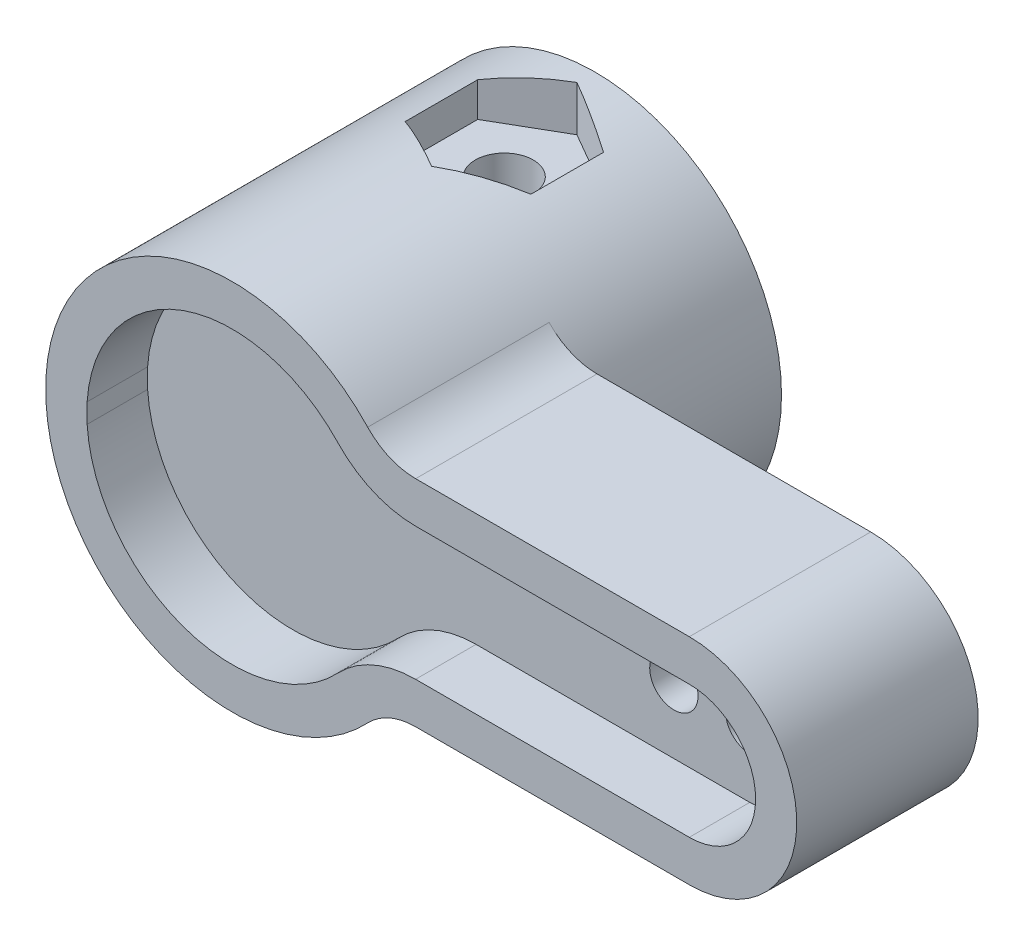
SolidWorks part; units mm, degrees
ref_plane "Front Plane" through (0, 0, 0) normal (0, 0, 1) x (1, 0, 0)
ref_plane "Top Plane" through (0, 0, 0) normal (0, 1, 0) x (1, 0, 0)
ref_plane "Right Plane" through (0, 0, 0) normal (1, 0, 0) x (0, 0, -1)
sketch "Sketch4" plane through (0, 0, 0) normal (0, 0, 1) x (1, 0, 0)
  line L0 (27.6867, 9.4129) -> (31.6042, 9.4129) construction
  line L1 (31.6042, 8.4129) -> (27.6867, 8.4129) construction
  line L2 (20.2537, 8.4129) -> (16.7375, 8.4129) construction
  line L3 (33.601, 5.8129) -> (47.9702, 5.8129)
  line L4 (47.9702, 12.0129) -> (33.601, 12.0129)
  line L5 (16.7375, 9.4129) -> (20.2537, 9.4129) construction
  line L6 (16.7375, 9.4129) -> (16.7375, 8.4129)
  line L7 (16.3565, 9.4259) -> (16.3565, 8.3999)
  line L8 (33.601, 5.4319) -> (47.9702, 5.4319)
  line L9 (47.9702, 12.3939) -> (33.601, 12.3939)
  line L10 (14.1975, 9.494) -> (14.1975, 8.3318)
  line L11 (33.601, 3.2729) -> (47.9702, 3.2729)
  line L12 (47.9702, 14.5529) -> (33.601, 14.5529)
  arc A0 (27.6867, 9.4129) -> (20.2537, 9.4129) centre (23.9702, 8.9129) ccw construction
  arc A1 (31.6042, 8.4129) -> (31.6042, 9.4129) centre (32.4702, 8.9129) ccw construction
  arc A2 (20.2537, 8.4129) -> (27.6867, 8.4129) centre (23.9702, 8.9129) ccw construction
  arc A3 (16.7375, 8.4129) -> (29.2399, 3.9336) centre (23.9702, 8.9129) ccw
  arc A4 (33.601, 5.8129) -> (29.2399, 3.9336) centre (33.601, -0.1871) ccw
  arc A5 (47.9702, 5.8129) -> (47.9702, 12.0129) centre (47.9702, 8.9129) ccw
  arc A6 (29.2399, 13.8921) -> (33.601, 12.0129) centre (33.601, 18.0129) ccw
  arc A7 (29.2399, 13.8921) -> (16.7375, 9.4129) centre (23.9702, 8.9129) ccw
  arc A8 (16.3565, 8.3999) -> (29.5168, 3.672) centre (23.9702, 8.9129) ccw
  arc A9 (33.601, 5.4319) -> (29.5168, 3.672) centre (33.601, -0.1871) ccw
  arc A10 (47.9702, 5.4319) -> (47.9702, 12.3939) centre (47.9702, 8.9129) ccw
  arc A11 (29.5168, 14.1538) -> (33.601, 12.3939) centre (33.601, 18.0129) ccw
  arc A12 (29.5168, 14.1538) -> (16.3565, 9.4259) centre (23.9702, 8.9129) ccw
  arc A13 (14.1975, 8.3318) -> (31.0861, 2.1892) centre (23.9702, 8.9129) ccw
  arc A14 (33.601, 3.2729) -> (31.0861, 2.1892) centre (33.601, -0.1871) ccw
  arc A15 (47.9702, 3.2729) -> (47.9702, 14.5529) centre (47.9702, 8.9129) ccw
  arc A16 (31.0861, 15.6366) -> (33.601, 14.5529) centre (33.601, 18.0129) ccw
  arc A17 (31.0861, 15.6366) -> (14.1975, 9.494) centre (23.9702, 8.9129) ccw
  dimension "D1" = 0.381
  dimension "D2" = 2.54
extrude "Boss-Extrude3" add sketch "Sketch4" along normal blind 3.175 contours A16 A17 L10 A13 A14 L11 A15 L12 A12 A11 L9 A10 L8 A9 A8 L7 region at (20.7744, 17.6996, 0)
sketch "Sketch5" plane through (0, 0, 0) normal (0, 0, -1) x (-1, 0, 0)
  line L3 (-33.601, 14.5529) -> (-47.9702, 14.5529)
  line L4 (-47.9702, 3.2729) -> (-33.601, 3.2729)
  line L5 (-14.1975, 8.3318) -> (-14.1975, 9.494)
  line L6 (-33.601, 14.5529) -> (-47.9702, 14.5529)
  line L7 (-47.9702, 3.2729) -> (-33.601, 3.2729)
  line L8 (-14.1975, 8.3318) -> (-14.1975, 9.494)
  arc A5 (-33.601, 14.5529) -> (-31.0861, 15.6366) centre (-33.601, 18.0129) ccw
  arc A6 (-47.9702, 14.5529) -> (-47.9702, 3.2729) centre (-47.9702, 8.9129) ccw
  arc A7 (-31.0861, 2.1892) -> (-33.601, 3.2729) centre (-33.601, -0.1871) ccw
  arc A8 (-31.0861, 2.1892) -> (-14.1975, 8.3318) centre (-23.9702, 8.9129) ccw
  arc A9 (-14.1975, 9.494) -> (-31.0861, 15.6366) centre (-23.9702, 8.9129) ccw
  arc A10 (-33.601, 14.5529) -> (-31.0861, 15.6366) centre (-33.601, 18.0129) ccw
  arc A11 (-47.9702, 14.5529) -> (-47.9702, 3.2729) centre (-47.9702, 8.9129) ccw
  arc A12 (-31.0861, 2.1892) -> (-33.601, 3.2729) centre (-33.601, -0.1871) ccw
  arc A13 (-31.0861, 2.1892) -> (-14.1975, 8.3318) centre (-23.9702, 8.9129) ccw
  arc A14 (-14.1975, 9.494) -> (-31.0861, 15.6366) centre (-23.9702, 8.9129) ccw
  dimension "D1" = 0
extrude "Boss-Extrude4" add sketch "Sketch5" along normal blind 6.35
sketch "Sketch8" plane through (0, 0, -6.35) normal (0, 0, -1) x (-1, 0, 0)
  circle A0 centre (-47.9732, 8.9129) radius 1.27
  arc A1 (-47.9702, 14.5529) -> (-47.9702, 3.2729) centre (-47.9702, 8.9129) ccw construction
  arc A2 (-14.1975, 9.494) -> (-31.0861, 15.6366) centre (-23.9702, 8.9129) ccw construction
  circle A3 centre (-43.9854, 8.9129) radius 1.27
  point P7 (-53.6102, 8.9129)
  dimension "D1" = 2.54
  dimension "D2" = 24.003
  dimension "D3" = 3.9878
extrude "Cut-Extrude3" cut sketch "Sketch8" against normal up to next
sketch "Sketch9" plane through (0, 0, -6.35) normal (0, 0, -1) x (-1, 0, 0)
  line L1 (-18.3505, 3.2931) -> (-29.59, 3.2931)
  line L2 (-18.3505, 3.2931) -> (-18.3505, 14.5326)
  line L3 (-18.3505, 14.5326) -> (-29.59, 14.5326)
  line L4 (-29.59, 3.2931) -> (-29.59, 14.5326)
  line L5 (-18.3505, 3.2931) -> (-29.59, 14.5326) construction
  line L6 (-18.3505, 14.5326) -> (-29.59, 3.2931) construction
  circle A0 centre (-23.9702, 8.9129) radius 6.4135
  arc A1 (-14.1975, 9.494) -> (-31.0861, 15.6366) centre (-23.9702, 8.9129) ccw construction
  circle A2 centre (-23.9702, 8.9129) radius 9.79
  arc M10 (-31.0861, 2.1892) -> (-14.1975, 8.3318) centre (-23.9702, 8.9129) ccw
  line M11 (-14.1975, 8.3318) -> (-14.1975, 9.494)
  arc M12 (-14.1975, 9.494) -> (-31.0861, 15.6366) centre (-23.9702, 8.9129) ccw
  dimension "D1" = 12.827
  dimension "D2" = 11.2395
extrude "Boss-Extrude5" add sketch "Sketch9" along normal blind 9.525 contours A2 A0 L3 L2 L1 L4 M12 M10 M11 | A0 L3 L4 | L4 A0 | A0 L4 L1 | L1 A0 | A0 L1 L2 | L2 A0 | A0 L2 L3 | L3 A0 region at (19.1113, 4.054, -6.35) region at (23.9702, 2.9739, -6.35) region at (18.0312, 8.9129, -6.35) region at (28.8291, 4.054, -6.35) region at (19.1113, 13.7717, -6.35) region at (29.9092, 8.9129, -6.35) region at (23.9702, 14.8519, -6.35) region at (28.8291, 13.7717, -6.35) region at (14.4743, 8.9129, -6.35)
sketch "Sketch10" plane through (0, 0, 0) normal (0, 1, 0) x (1, 0, 0)
  line L1 (20.8797, 15.875) -> (27.0607, 15.875) construction
  line L3 (23.9702, 15.875) -> (23.9702, 6.35) construction
  line L4 (47.9702, 6.35) -> (33.601, 6.35) construction
  line L5 (20.8797, 15.875) -> (27.0607, 15.875) construction
  circle A0 centre (23.9702, 11.1125) radius 1.524
  point P16 (23.9702, 11.1125)
  dimension "D1" = 3.048
extrude "Cut-Extrude4" cut sketch "Sketch10" against normal through all both and the other way through all
ref_plane "Plane1" through (0, -0.8771, 0) normal (0, -1, 0) x (-1, 0, 0)
sketch "Sketch11" plane through (0, -0.8771, 0) normal (0, -1, 0) x (-1, 0, 0)
  circle A0 centre (-23.9702, 11.1125) radius 2.413
  dimension "D1" = 4.826
extrude "Cut-Extrude5" cut sketch "Sketch11" against normal blind 2.921
ref_plane "Plane2" through (0, 18.7029, 0) normal (0, 1, 0) x (1, 0, 0)
sketch "Sketch12" plane through (0, 18.7029, 0) normal (0, 1, 0) x (1, 0, 0)
  line L0 (31.0861, -3.175) -> (31.0861, 6.35) construction
  line L1 (27.2722, 9.2061) -> (27.2722, 13.0189)
  line L2 (27.2722, 13.0189) -> (23.9702, 14.9253)
  line L3 (23.9702, 14.9253) -> (20.6682, 13.0189)
  line L4 (20.6682, 13.0189) -> (20.6682, 9.2061)
  line L5 (20.6682, 9.2061) -> (23.9702, 7.2997)
  line L6 (23.9702, 7.2997) -> (27.2722, 9.2061)
  circle A0 centre (23.9702, 11.1125) radius 3.302 construction
  dimension "D1" = 6.604
extrude "Cut-Extrude6" cut sketch "Sketch12" against normal blind 2.3813
